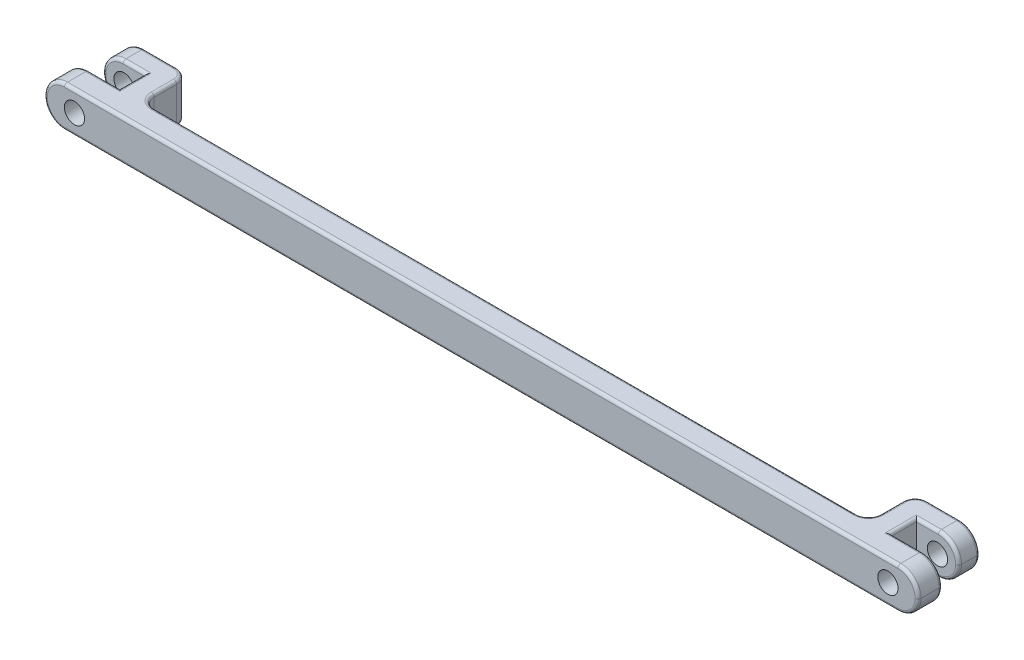
SolidWorks part; units mm, degrees
material "A286 Iron Base Superalloy"
ref_plane "Front Plane" through (0, 0, 0) normal (0, 0, 1) x (1, 0, 0)
ref_plane "Top Plane" through (0, 0, 0) normal (0, 1, 0) x (1, 0, 0)
ref_plane "Right Plane" through (0, 0, 0) normal (1, 0, 0) x (0, 0, -1)
sketch "Sketch2" plane through (0, 0, 0) normal (0, 1, 0) x (1, 0, 0)
  line L0 (-723, 0) -> (723, 0)
  line L1 (723, 0) -> (723, 40)
  line L2 (723, 40) -> (638, 40)
  line L3 (638, 40) -> (638, 82)
  line L4 (638, 82) -> (708, 82)
  line L5 (708, 82) -> (708, 117)
  line L6 (708, 117) -> (601, 117)
  line L7 (601, 117) -> (601, 40)
  line L8 (601, 40) -> (-601, 40)
  line L9 (673, 117) -> (673, 0) construction
  line L10 (601, 40) -> (600.3376, 40.4117)
  line L11 (0, 0) -> (0, 256.4103) construction
  line L13 (-601, 40) -> (-600.3376, 40.4117)
  line L14 (-601, 117) -> (-601, 40)
  line L15 (-708, 117) -> (-601, 117)
  line L16 (-708, 82) -> (-708, 117)
  line L17 (-638, 82) -> (-708, 82)
  line L18 (-638, 40) -> (-638, 82)
  line L19 (-723, 40) -> (-638, 40)
  line L20 (-723, 0) -> (-723, 40)
  point P19 (0, 40)
  dimension "D1" = 723
  dimension "D2" = 40
  dimension "D3" = 35
  dimension "D4" = 42
  dimension "D5" = 90
  dimension "D6" = 35
  dimension "D7" = 85
  dimension "D8" = 70
  dimension "D9" = 107
  dimension "D10" = 40
extrude "Boss-Extrude1" add sketch "Sketch2" along normal blind 67 contours L0 L11 L8 L14 L15 L16 L17 L18 L19 L20 | L11 L0 L1 L2 L3 L4 L5 L6 L7 L8 region at (-405.2832, 0, -30.5626) region at (405.2832, 0, -30.5626)
sketch "Sketch3" plane through (0, 0, -117) normal (0, 0, -1) x (-1, 0, 0)
  line L0 (-708, 67) -> (-708, 0) construction
  line L1 (-708, 67) -> (-601, 67) construction
  line L2 (0, 0) -> (0, 101.5751) construction
  circle A0 centre (-673, 33.5) radius 16.75
  circle A1 centre (673, 33.5) radius 16.75
  point P2 (-708, 33.5)
  dimension "D1" = 35
  dimension "D3" = 33.5
  dimension "D2" = 33.5
extrude "Cut-Extrude2" cut sketch "Sketch3" against normal up to surface (117 mm away) up to face at (0, 33.5, 0)
fillet "Radyus1" radius 20 4 edges at (601, 33.5, -117) (601, 33.5, -40) (-601, 33.5, -117) (-601, 33.5, -40)
fillet "Radyus2" radius 33.5 8 edges at (-723, 0, -20) (-723, 67, -20) (723, 0, -20) (723, 67, -20) (708, 67, -99.5) (708, 0, -99.5) (-708, 0, -99.5) (-708, 67, -99.5)
fillet "Radyus4" radius 5 46 edges at (698.1881, 57.1881, -117) (698.1881, 9.8119, -117) (647.75, 0, -117) (606.8579, 0, -111.1421) (601, 0, -78.5) (595.1421, 0, -45.8579) (0, 0, -40) (-595.1421, 0, -45.8579) (-601, 0, -78.5) (-606.8579, 0, -111.1421) (-647.75, 0, -117) (-698.1881, 9.8119, -117) (-698.1881, 57.1881, -117) (713.1881, 57.1881, -40) (713.1881, 9.8119, -40) (663.75, 0, -40) (656.25, 0, -82) (698.1881, 9.8119, -82) (698.1881, 57.1881, -82) (-713.1881, 57.1881, 0) (-713.1881, 9.8119, 0) (0, 0, 0) (713.1881, 9.8119, 0) (713.1881, 57.1881, 0) (-713.1881, 57.1881, -40) (-713.1881, 9.8119, -40) (-663.75, 0, -40) (-656.25, 0, -82) (-698.1881, 9.8119, -82) (-698.1881, 57.1881, -82) (-638, 67, -61) (-656.25, 67, -82) (-647.75, 67, -117) (-606.8579, 67, -111.1421) (-601, 67, -78.5) (-595.1421, 67, -45.8579) (0, 67, -40) (595.1421, 67, -45.8579) (601, 67, -78.5) (606.8579, 67, -111.1421) (647.75, 67, -117) (656.25, 67, -82) (638, 67, -61) (663.75, 67, -40) (0, 67, 0) (-663.75, 67, -40)
